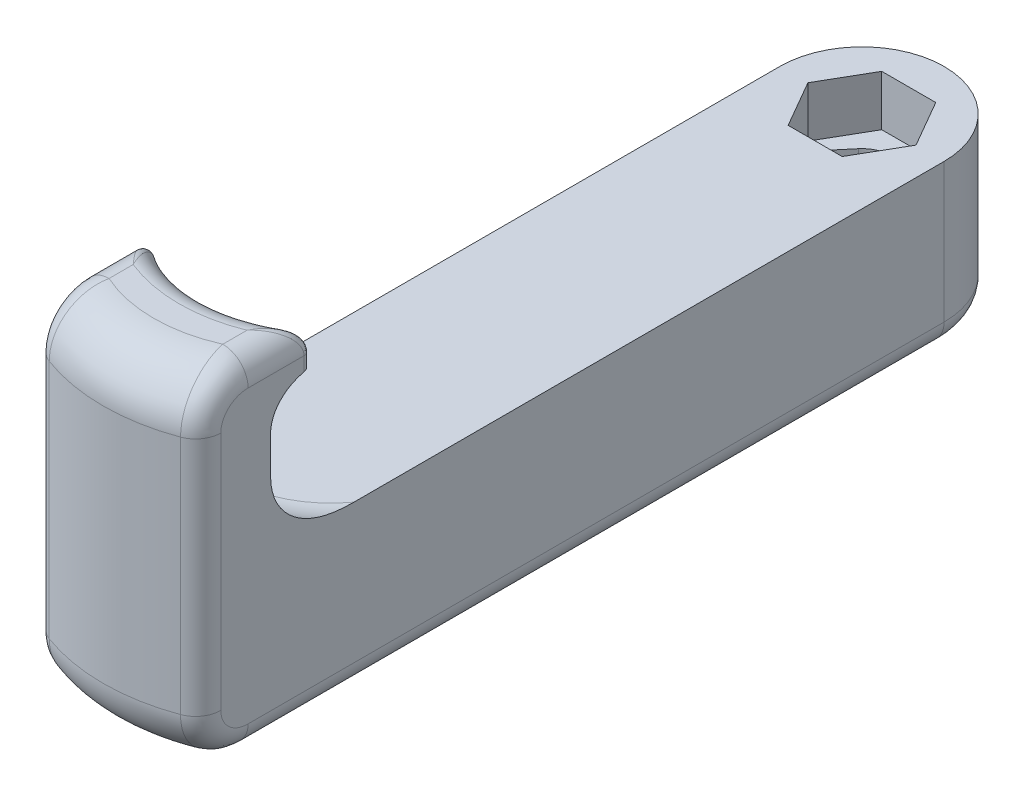
SolidWorks part; units mm, degrees
ref_plane "Ebene vorne" through (0, 0, 0) normal (0, 0, 1) x (1, 0, 0)
ref_plane "Ebene oben" through (0, 0, 0) normal (0, 1, 0) x (1, 0, 0)
ref_plane "Ebene rechts" through (0, 0, 0) normal (1, 0, 0) x (0, 0, -1)
sketch "Skizze1" plane through (0, 0, 0) normal (0, 1, 0) x (1, 0, 0)
  line L0 (-6.5, 60) -> (-6.5, 1.4815)
  line L1 (0, 0) -> (0, 19.7505) construction
  line L2 (6.5, 60) -> (6.5, 1.4815)
  line L3 (-6.5, 60) -> (6.5, 60)
  circle A0 centre (0, 60) radius 6.5
  circle A2 centre (0, 15) radius 15
  circle A3 centre (0, 60) radius 2.3
  dimension "D4" = 30
  dimension "D2" = 13
  dimension "D5" = 4.6
  dimension "D1" = 0
  dimension "D3" = 60
extrude "Aufsatz-Linear austragen2" add sketch "Skizze1" along normal blind 13 contours A2 L1 L0 | L1 A2 L2 | L1 A2 L2 A0 | A2 L1 A0 L0 | A0 L1 A3 L3 | L1 A0 L3 A3 | L1 A3 L3 A0 | A3 L1 A0 L3 | A3 region at (0, 0, -42.2433) region at (0, 0, -63.0138) region at (0, 0, -56.9862) region at (0, 0, -29.673)
sketch "Skizze2" plane through (0, 13, 0) normal (0, 1, 0) x (1, 0, 0)
  line L0 (0, 66.5) -> (0, 0) construction
  line L1 (-6.5, 15) -> (6.5, 15)
  line L2 (-6.5, 60) -> (-6.5, 1.4815) construction
  line L3 (6.5, 60) -> (6.5, 1.4815) construction
  line L4 (-6.5, 15) -> (-6.5, 1.4815)
  line L5 (6.5, 15) -> (6.5, 1.4815)
  arc A0 (6.5, 60) -> (-6.5, 60) centre (0, 60) ccw construction
  arc A1 (-6.5, 1.4815) -> (6.5, 1.4815) centre (0, 15) ccw construction
  circle A2 centre (0, 15) radius 15
  line M3 (-6.5, 60) -> (-6.5, 1.4815)
  arc M4 (-6.5, 1.4815) -> (6.5, 1.4815) centre (0, 15) ccw
  line M5 (6.5, 1.4815) -> (6.5, 60)
  dimension "D1" = 15
extrude "Aufsatz-Linear austragen3" add sketch "Skizze2" along normal blind 14 contours L1 L0 A2 M5 | L0 L1 M3 M4 region at (3.1953, 13, -7.7352) region at (-3.1953, 13, -7.7352)
sketch "Skizze5" plane through (0, 0, 0) normal (1, 0, 0) x (0, 0, -1)
  line L0 (5, 18) -> (5, 21)
  line L2 (18, 27) -> (18, 13)
  line L3 (18, 13) -> (10, 13)
  line L11 (1.4815, 27) -> (15, 27) construction
  line L12 (8, 27) -> (18, 27)
  line L13 (8, 24) -> (8, 27)
  line L14 (60, 13) -> (15, 13) construction
  line L15 (60, 13) -> (60, 0) construction
  arc A0 (8, 24) -> (5, 21) centre (8, 21) ccw
  arc A1 (5, 18) -> (10, 13) centre (10, 18) ccw
  point P6 (6.9283, 24)
  point P11 (6.9467, 20.9353)
  dimension "D1" = 3
  dimension "D2" = 5
  dimension "D3" = 11
  dimension "D4" = 13
  dimension "D5" = 90
  dimension "D6" = 5
  dimension "D7" = 55
revolve "Schnitt-Rotation1" cut sketch "Skizze5" angle 360 about L2
extrude "Schnitt-Linear austragen1" cut sketch "Skizze1<5>" along normal blind 14 contours L1 L3 A3 | L3 L1 A3 | A3 L1 L3 | L1 A3 L3 region at (0, 0, -60.9762) region at (0, 0, -59.0238)
sketch "Skizze1<5>" plane through (0, 0, 0) normal (0, 1, 0) x (1, 0, 0) same geometry as "Skizze1"
fillet "Verrundung1" radius 0.5 2 edges at (-6.5, 25.5, -10.4007) (6.5, 25.5, -10.4007)
fillet "Verrundung2" radius 4 2 edges at (0, 0, 0) (0, 27, 0)
sketch "Skizze7" plane through (0, 13, 0) normal (0, 1, 0) x (1, 0, 0)
  line L0 (-4.2724, 60) -> (4.2724, 60) construction
  line L1 (2.1362, 63.7) -> (-2.1362, 63.7)
  line L2 (-2.1362, 63.7) -> (-4.2724, 60)
  line L3 (-4.2724, 60) -> (-2.1362, 56.3)
  line L4 (-2.1362, 56.3) -> (2.1362, 56.3)
  line L5 (2.1362, 56.3) -> (4.2724, 60)
  line L6 (4.2724, 60) -> (2.1362, 63.7)
  circle A1 centre (0, 60) radius 3.7 construction
  dimension "D1" = 7.4
extrude "Schnitt-Linear austragen3" cut sketch "Skizze7" against normal blind 4
sketch "Skizze8" plane through (0, 9, 0) normal (0, 1, 0) x (1, 0, 0)
  line L0 (0, 60) -> (-3.0024, 60)
  line L1 (-3.0024, 60) -> (-1.7619, 61.4784)
  line L2 (-3.0024, 60) -> (-1.7619, 58.5216)
  line L3 (-1.7619, 61.4784) -> (-1.7619, 58.5216)
  circle A0 centre (0, 60) radius 2.3 construction
  circle M3 centre (0, 60) radius 2.3
  dimension "D1" = 100
extrude "Schnitt-Linear austragen4" cut sketch "Skizze8" against normal blind 20 contours L0 L2 M3 | L1 L0 M3 | L3 L0 M3 | L3 L0 M3 region at (-1.9795, 9, -59.4358) region at (-1.9795, 9, -60.5642) region at (-2.4614, 9, -59.6114) region at (-2.4614, 9, -60.3886)
fillet "Verrundung5" radius 2 14 edges at (6.5, 0, -33.0629) (6.5, 1.6996, -2.2937) (6.5, 13.5, -1.4815) (6.5, 25.8728, -2.8456) (6.5, 27, -7.7545) (6.2315, 27, -9.8264) (0, 27, -8) (-6.2315, 27, -9.8264) (-6.5, 27, -7.7545) (-6.5, 25.3004, -2.2937) (-6.5, 13.5, -1.4815) (-6.5, 1.1272, -2.8456) (-6.5, 0, -33.0629) (0, 0, -66.5)
